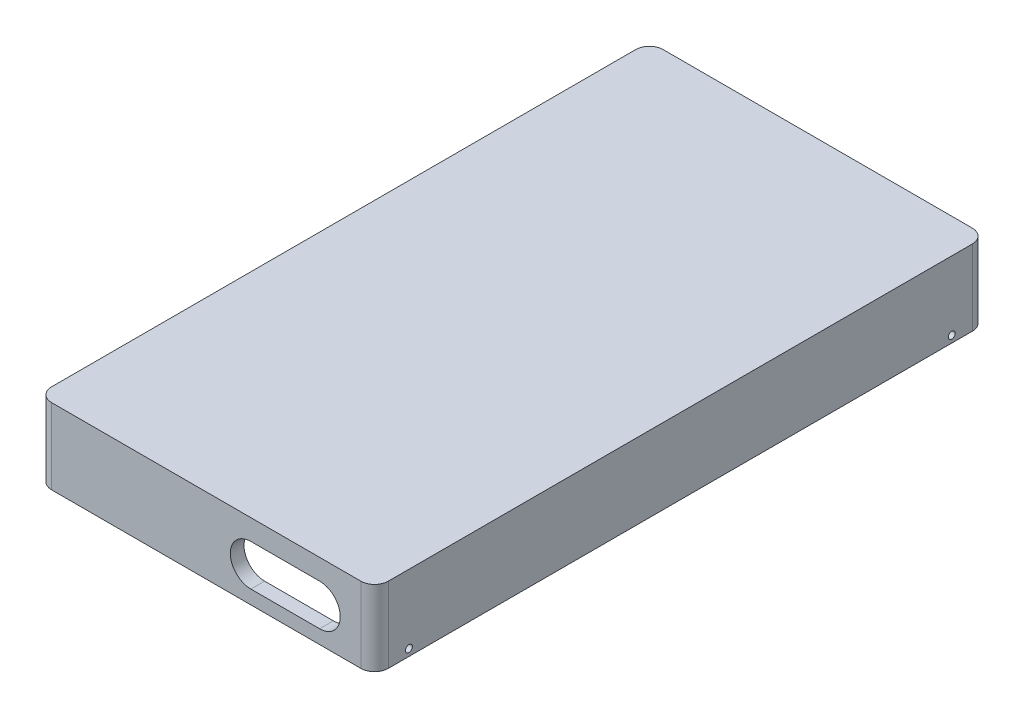
SolidWorks part; units mm, degrees
ref_plane "Front Plane" through (0, 0, 0) normal (0, 0, 1) x (1, 0, 0)
ref_plane "Top Plane" through (0, 0, 0) normal (0, 1, 0) x (1, 0, 0)
ref_plane "Right Plane" through (0, 0, 0) normal (1, 0, 0) x (0, 0, -1)
sketch "Sketch1" plane through (0, 0, 0) normal (0, 1, 0) x (1, 0, 0)
  line L1 (0, 0) -> (57.15, 0)
  line L2 (0, 0) -> (0, 107.95)
  line L3 (0, 107.95) -> (57.15, 107.95)
  line L4 (57.15, 0) -> (57.15, 107.95)
  dimension "D1" = 107.95
  dimension "D2" = 57.15
extrude "Boss-Extrude1" add sketch "Sketch1" along normal blind 2.54
sketch "Sketch2" plane through (0, 2.54, 0) normal (0, 1, 0) x (1, 0, 0)
  line L0 (0, 53.975) -> (57.15, 53.975) construction
  line L1 (0, 107.95) -> (0, 0) construction
  line L2 (57.15, 0) -> (57.15, 107.95) construction
  line L3 (28.575, 107.95) -> (28.575, 0) construction
  line L4 (57.15, 107.95) -> (0, 107.95) construction
  line L5 (0, 0) -> (57.15, 0) construction
  line L7 (-2.54, -2.54) -> (59.69, -2.54)
  line L8 (-2.54, -2.54) -> (-2.54, 110.49)
  line L9 (-2.54, 110.49) -> (59.69, 110.49)
  line L10 (59.69, -2.54) -> (59.69, 110.49)
  line L11 (-2.54, -2.54) -> (59.69, 110.49) construction
  line L12 (-2.54, 110.49) -> (59.69, -2.54) construction
  line L13 (0, 0) -> (57.15, 0)
  line L14 (0, 0) -> (0, 107.95)
  line L15 (0, 107.95) -> (57.15, 107.95)
  line L16 (57.15, 0) -> (57.15, 107.95)
  line L17 (0, 0) -> (57.15, 107.95) construction
  line L18 (0, 107.95) -> (57.15, 0) construction
  point P12 (28.575, 53.975)
  point P17 (28.575, 53.975)
  dimension "D1" = 2.54
  dimension "D2" = 2.54
extrude "Boss-Extrude3" add sketch "Sketch2" against normal blind 13.97
sketch "Sketch3" plane through (0, 0, 2.54) normal (0, 0, 1) x (1, 0, 0)
  line L0 (-2.54, -5.08) -> (59.69, -5.08) construction
  line L1 (-2.54, -11.43) -> (-2.54, 2.54) construction
  line L2 (59.69, -11.43) -> (59.69, 2.54) construction
  line L3 (28.575, 2.54) -> (28.575, -11.43) construction
  line L4 (-2.54, 2.54) -> (59.69, 2.54) construction
  line L5 (-2.54, -11.43) -> (59.69, -11.43) construction
  line L6 (36.83, -5.08) -> (49.53, -5.08) construction
  line L7 (36.83, -1.27) -> (49.53, -1.27)
  line L8 (36.83, -8.89) -> (49.53, -8.89)
  arc A0 (36.83, -1.27) -> (36.83, -8.89) centre (36.83, -5.08) ccw
  arc A1 (49.53, -8.89) -> (49.53, -1.27) centre (49.53, -5.08) ccw
  point P4 (8.5223, -5.715)
  point P5 (0, 0)
  point P14 (43.18, -5.08)
  point P19 (65.5456, -5.715)
  point P20 (0, 0)
  dimension "D1" = 39.37
  dimension "D2" = 12.7
  dimension "D3" = 7.62
  dimension "D4" = 7.62
extrude "Cut-Extrude1" cut sketch "Sketch3" against normal blind 10.16
fillet "Fillet1" radius 2.54 4 edges at (-2.54, -4.445, -110.49) (59.69, -4.445, -110.49) (59.69, -4.445, 2.54) (-2.54, -4.445, 2.54)
sketch "Sketch4" plane through (-2.54, 0, 0) normal (-1, 0, 0) x (0, 0, 1)
  line L0 (-107.95, -10.16) -> (0, -10.16) construction
  line L1 (-107.95, 2.54) -> (-107.95, -11.43) construction
  line L2 (0, -11.43) -> (0, 2.54) construction
  line L3 (-107.95, -11.43) -> (0, -11.43) construction
  line L4 (-53.975, 2.54) -> (-53.975, -11.43) construction
  line L5 (-107.95, 2.54) -> (0, 2.54) construction
  circle A0 centre (-104.14, -10.16) radius 0.635
  circle A1 centre (-3.81, -10.16) radius 0.635
  dimension "D2" = 1.27
  dimension "D3" = 3.81
  dimension "D1" = 1.27
extrude "Cut-Extrude2" cut sketch "Sketch4" against normal through all
